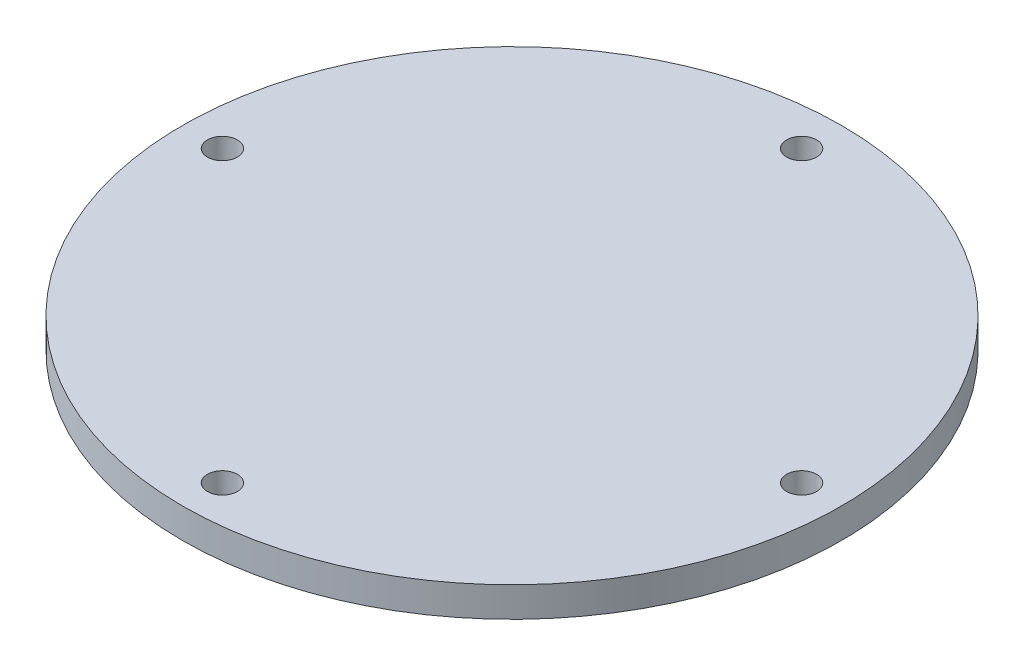
SolidWorks part; units mm, degrees
ref_plane "Front Plane" through (0, 0, 0) normal (0, 0, 1) x (1, 0, 0)
ref_plane "Top Plane" through (0, 0, 0) normal (0, 1, 0) x (1, 0, 0)
ref_plane "Right Plane" through (0, 0, 0) normal (1, 0, 0) x (0, 0, -1)
sketch "Sketch1" plane through (0, 0, 0) normal (0, 1, 0) x (1, 0, 0)
  circle A0 centre (0, 0) radius 33
  circle A1 centre (-29, 0) radius 1.5
  circle A2 centre (0, 0) radius 29 construction
  circle A3 centre (0, 29) radius 1.5
  circle A4 centre (29, 0) radius 1.5
  circle A5 centre (0, -29) radius 1.5
  point P6 (27.2253, 0)
  point P7 (0, 0)
  point P8 (0, 0)
  point P15 (0, 0)
  point P16 (0, 0)
  point P17 (0, 0)
  dimension "D1" = 66
  dimension "D2" = 4
  dimension "D3" = 3
  dimension "D4" = 4
extrude "Boss-Extrude1" add sketch "Sketch1" along normal blind 3
